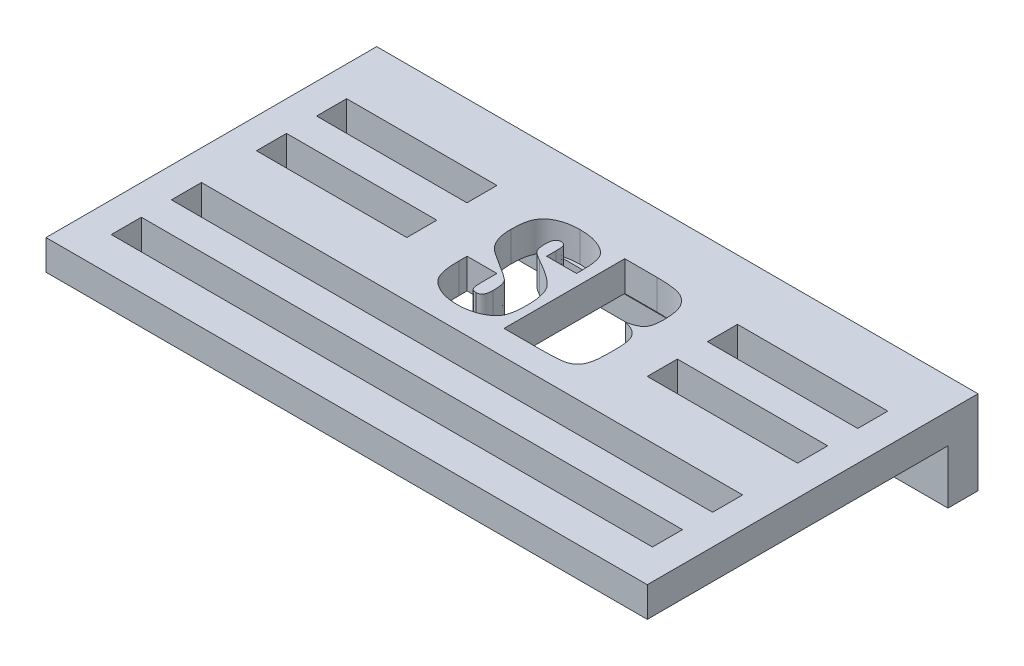
SolidWorks part; units mm, degrees
ref_plane "Front Plane" through (0, 0, 0) normal (0, 0, 1) x (1, 0, 0)
ref_plane "Top Plane" through (0, 0, 0) normal (0, 1, 0) x (1, 0, 0)
ref_plane "Right Plane" through (0, 0, 0) normal (1, 0, 0) x (0, 0, -1)
sketch "Sketch1" plane through (0, 0, 0) normal (0, 1, 0) x (1, 0, 0)
  line L1 (1057.3387, 602.5672) -> (1157.3387, 602.5672)
  line L2 (1057.3387, 602.5672) -> (1057.3387, 552.5672)
  line L3 (1057.3387, 552.5672) -> (1157.3387, 552.5672)
  line L4 (1157.3387, 602.5672) -> (1157.3387, 552.5672)
  dimension "D1" = 50
  dimension "100" = 100
extrude "Boss-Extrude1" add sketch "Sketch1" along normal blind 5
sketch "Sketch2" plane through (0, 0, -602.5672) normal (0, 0, -1) x (-1, 0, 0)
  line L1 (-1057.3387, 5) -> (-1157.3387, 5)
  line L2 (-1057.3387, 5) -> (-1057.3387, -8.9796)
  line L3 (-1057.3387, -8.9796) -> (-1157.3387, -8.9796)
  line L4 (-1157.3387, 5) -> (-1157.3387, -8.9796)
extrude "Boss-Extrude2" add sketch "Sketch2" along normal blind 5
sketch "Sketch3" plane through (0, 5, 0) normal (0, 1, 0) x (1, 0, 0)
  line L0 (1057.3387, 607.5672) -> (1157.3387, 607.5672) construction
  line L1 (1062.3387, 597.5672) -> (1087.3387, 597.5672)
  line L2 (1062.3387, 597.5672) -> (1062.3387, 592.5672)
  line L3 (1062.3387, 592.5672) -> (1087.3387, 592.5672)
  line L4 (1087.3387, 597.5672) -> (1087.3387, 592.5672)
  line L5 (1057.3387, 552.5672) -> (1157.3387, 552.5672) construction
  line L6 (1057.3387, 607.5672) -> (1057.3387, 552.5672) construction
  line L7 (1127.3387, 597.5672) -> (1127.3387, 592.5672)
  line L8 (1127.3387, 597.5672) -> (1152.3387, 597.5672)
  line L9 (1152.3387, 597.5672) -> (1152.3387, 592.5672)
  line L10 (1127.3387, 592.5672) -> (1152.3387, 592.5672)
  line L11 (1127.3387, 587.5672) -> (1127.3387, 582.5672)
  line L12 (1127.3387, 587.5672) -> (1152.3387, 587.5672)
  line L13 (1152.3387, 587.5672) -> (1152.3387, 582.5672)
  line L14 (1127.3387, 582.5672) -> (1152.3387, 582.5672)
  line L15 (1062.3387, 587.5672) -> (1062.3387, 582.5672)
  line L16 (1062.3387, 587.5672) -> (1087.3387, 587.5672)
  line L17 (1087.3387, 587.5672) -> (1087.3387, 582.5672)
  line L18 (1062.3387, 582.5672) -> (1087.3387, 582.5672)
  line L19 (1157.3387, 552.5672) -> (1157.3387, 607.5672) construction
  line L20 (1062.3387, 563.4231) -> (1062.3387, 558.4231)
  line L21 (1062.3387, 573.4231) -> (1152.3387, 573.4231)
  line L22 (1062.3387, 573.4231) -> (1062.3387, 568.4231)
  line L23 (1062.3387, 568.4231) -> (1152.3387, 568.4231)
  line L24 (1152.3387, 573.4231) -> (1152.3387, 568.4231)
  line L25 (1062.3387, 563.4231) -> (1152.3387, 563.4231)
  line L26 (1152.3387, 563.4231) -> (1152.3387, 558.4231)
  line L27 (1062.3387, 558.4231) -> (1152.3387, 558.4231)
  text T0 "SB" font "Impact" height in points 72
  dimension "D1" = 10
  dimension "D2" = 25
  dimension "5" = 5
  dimension "D3" = 37
  dimension "D4" = 25
  dimension "D5" = 5
  dimension "D8" = 5
  dimension "D9" = 5
  dimension "D6" = 2
  dimension "D7" = 2
  dimension "D10" = 2
extrude "Cut-Extrude1" cut sketch "Sketch3" against normal up to surface (5 mm away) up to face at (1107.3387, 0, -577.5672)
sketch "Sketch4" plane through (0, 0, -607.5672) normal (0, 0, -1) x (-1, 0, 0)
  line L0 (-1063.3387, -2.9796) -> (-1151.3387, -2.9796) construction
  line L1 (-1063.3387, -5.0296) -> (-1151.3387, -5.0296)
  line L2 (-1063.3387, -0.9296) -> (-1151.3387, -0.9296)
  line L3 (-1157.3387, -8.9796) -> (-1057.3387, -8.9796) construction
  line L4 (-1057.3387, -8.9796) -> (-1057.3387, 5) construction
  line L5 (-1157.3387, 5) -> (-1157.3387, -8.9796) construction
  arc A0 (-1063.3387, -5.0296) -> (-1063.3387, -0.9296) centre (-1063.3387, -2.9796) ccw
  arc A1 (-1151.3387, -0.9296) -> (-1151.3387, -5.0296) centre (-1151.3387, -2.9796) ccw
  point P2 (-1107.3387, -2.9796)
  dimension "D1" = 4.1
  dimension "D2" = 6
  dimension "D3" = 6
  dimension "D4" = 6
extrude "Cut-Extrude2" cut sketch "Sketch4" against normal up to surface (5 mm away) up to face at (1107.3387, -4.4898, -602.5672)
sketch "Sketch5" plane through (0, 5, 0) normal (0, 1, 0) x (1, 0, 0)
  line L1 (1111.29, 596.2204) -> (1116.8191, 596.2204)
  line L2 (1111.29, 596.2204) -> (1111.29, 580.2212)
  line L3 (1111.29, 580.2212) -> (1116.8191, 580.2212)
  line L4 (1116.8191, 596.2204) -> (1116.8191, 580.2212)
extrude "Cut-Extrude3" cut sketch "Sketch5" against normal blind 5
